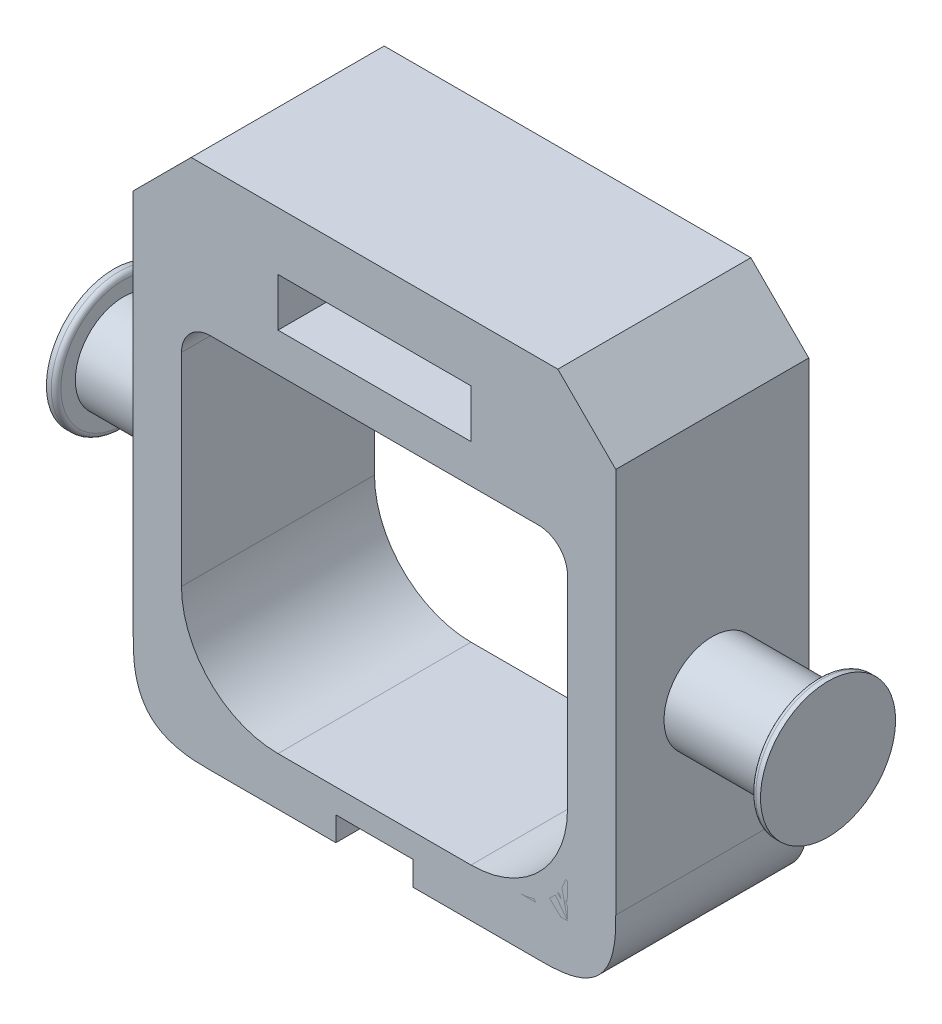
SolidWorks part; units mm, degrees
ref_plane "Front Plane" through (0, 0, 0) normal (0, 0, 1) x (1, 0, 0)
ref_plane "Top Plane" through (0, 0, 0) normal (0, 1, 0) x (1, 0, 0)
ref_plane "Right Plane" through (0, 0, 0) normal (1, 0, 0) x (0, 0, -1)
sketch "Sketch1" plane through (0, 0, 0) normal (0, 0, 1) x (1, 0, 0)
  line L0 (-20, 0) -> (0, 0)
  line L1 (0, 0) -> (0, -17)
  line L2 (0, -17) -> (-20, -17)
  line L3 (-20, -17) -> (-20, 0)
  line L4 (-22.5, 7.5) -> (-22.5, -19.5)
  line L5 (-22.5, -19.5) -> (2.5, -19.5)
  line L6 (2.5, -19.5) -> (2.5, 7.5)
  line L7 (-22.5, 7.5) -> (2.5, 7.5)
  dimension "D1" = 20
  dimension "D2" = 17
  dimension "D3" = 7.5
  dimension "D4" = 27
  dimension "D5" = 25
  dimension "D6" = 2.5
extrude "Boss-Extrude1" add sketch "Sketch1" along normal blind 10
fillet "Fillet1" radius 4 2 edges at (-22.5, -19.5, 5) (2.5, -19.5, 5) curvature continuous yes
ref_plane "Plane1" through (-20, -17, 10) normal (0, -1, 0) x (-1, 0, 0)
sketch "Sketch3" plane through (0, 0, 10) normal (0, 0, 1) x (1, 0, 0)
  line L1 (0, 0) -> (-10, -17)
  line L2 (-21.65, -17) -> (-18.35, -17) construction
  line L3 (-20, 0) -> (-20, -1.5)
  line L4 (-20, 0) -> (-20, -17) construction
  line L5 (-20, 0) -> (-18.5, 0)
  arc A0 (-20, -1.5) -> (-18.5, 0) centre (-18.5, -1.5) cw
  line M13 (-20, -17) -> (-20, 0)
  line M14 (-20, 0) -> (0, 0)
extrude "Boss-Extrude2" add sketch "Sketch3" against normal blind 10 contours A0 M13 M14 region at (-19.6649, -0.3351, 10)
sketch "Sketch4" plane through (0, 0, 10) normal (0, 0, 1) x (1, 0, 0)
  line L0 (0, 0) -> (0, -1.4954)
  line L1 (0, -17) -> (0, 0) construction
  line L2 (0, 0) -> (-1.4954, 0)
  line L3 (0, 0) -> (-18.5, 0) construction
  arc A0 (0, -1.4954) -> (-1.4954, 0) centre (-1.4954, -1.4954) ccw
extrude "Boss-Extrude3" add sketch "Sketch4" against normal blind 10
sketch "Sketch6" plane through (0, 0, 10) normal (0, 0, 1) x (1, 0, 0)
  line L0 (0, -17) -> (0, -14.5)
  line L1 (0, -17) -> (0, -1.4954) construction
  line L2 (0, -17) -> (-2.5, -17)
  line L3 (-20, -17) -> (0, -17) construction
  arc A0 (-2.5, -17) -> (0, -14.5) centre (-2.5, -14.5) ccw
extrude "Boss-Extrude4" add sketch "Sketch6" against normal blind 7.5 separate body
sketch "Sketch7" plane through (0, 0, 10) normal (0, 0, 1) x (1, 0, 0)
  line L0 (-20, -17) -> (-15, -17)
  line L1 (-21.65, -17) -> (-18.35, -17) construction
  line L2 (-20, -1.5) -> (-20, -17) construction
  line L3 (-20, -17) -> (-20, -12)
  line L4 (0, -17) -> (-5, -17)
  line L5 (-20, -17) -> (0, -17) construction
  line L6 (0, -17) -> (0, -12)
  line L7 (0, -17) -> (0, -1.4954) construction
  arc A0 (-15, -17) -> (-20, -12) centre (-15, -12) cw
  arc A1 (-5, -17) -> (0, -12) centre (-5, -12) ccw
extrude "Boss-Extrude5" add sketch "Sketch7" against normal blind 10
chamfer "Chamfer1" distance 3 angle 45 2 edges at (2.5, 7.5, 5) (-22.5, 7.5, 5)
sketch "Sketch8" plane through (0, 0, 10) normal (0, 0, 1) x (1, 0, 0)
  line L0 (-15, 4.5) -> (-5, 4.5)
  line L1 (-5, 4.5) -> (-5, 2)
  line L2 (-5, 2) -> (-15, 2)
  line L3 (-15, 2) -> (-15, 4.5)
  line L4 (-0.5, 7.5) -> (-19.5, 7.5) construction
  line L8 (-22.5, 4.5) -> (-22.5, -15.5) construction
  dimension "D1" = 7.5
  dimension "D2" = 3
  dimension "D3" = 2.5
extrude "Cut-Extrude1" cut sketch "Sketch8" against normal blind 10.5 contours L3 L2 L1 L0 region at (-10, 3.25, 10)
sketch "Sketch9" plane through (0, 0, 10) normal (0, 0, 1) x (1, 0, 0)
  line L0 (-18.5, -19.5) -> (-1.5, -19.5) construction
  line L1 (-6.1419, -18.5) -> (-4.1419, -18.5)
  line L2 (-6.1419, -18.5) -> (-6.1419, -19.5)
  line L3 (-6.1419, -19.5) -> (-4.1419, -19.5)
  line L4 (-4.1419, -18.5) -> (-4.1419, -19.5)
  dimension "D1" = 1
sketch "Sketch12" plane through (0, 0, 0) normal (0, 0, -1) x (-1, 0, 0)
  line L10 (19.5, 7.5) -> (0.5, 7.5)
  line L11 (0.5, 7.5) -> (-2.5, 4.5)
  line L12 (-2.5, 4.5) -> (-2.5, -15.5)
  line L13 (1.5, -19.5) -> (18.5, -19.5)
  line L14 (22.5, -15.5) -> (22.5, 4.5)
  line L15 (22.5, 4.5) -> (19.5, 7.5)
  line L18 (-2.5, 4.5) -> (-2.5, -15.5)
  spline S2 degree 2 poles (67.845, 982.0209) (-3.6492, 1.7622) (-2.4812, -16.3302) (-2.4524, -16.7775) (-2.3691, -17.1519) (-2.1636, -18.0767) (-1.6244, -18.6183) (-1.0848, -19.1602) (-0.1577, -19.3678) (0.2161, -19.4515) (0.6646, -19.4809) (18.738, -20.6634) (998.9799, 51.3297) knots -7.651516 -7.651516 -7.651516 0.125 0.125 0.25 0.25 0.5 0.5 0.75 0.75 0.875 0.875 8.610168 8.610168 8.610168 only from (-2.5, -15.5) to (1.5, -19.5)
  spline S3 degree 2 poles (-979.0209, 50.845) (1.2378, -20.6492) (19.3302, -19.4812) (19.7775, -19.4524) (20.1519, -19.3691) (21.0767, -19.1636) (21.6183, -18.6244) (22.1602, -18.0848) (22.3678, -17.1577) (22.4515, -16.7839) (22.4809, -16.3354) (23.6634, 1.738) (-48.3297, 981.9799) knots -7.651516 -7.651516 -7.651516 0.125 0.125 0.25 0.25 0.5 0.5 0.75 0.75 0.875 0.875 8.610168 8.610168 8.610168 only from (18.5, -19.5) to (22.5, -15.5)
  dimension "D1" = 0
ref_plane "Plane2" through (-10, 0, 0) normal (-1, 0, 0) x (0, 0, 1)
sketch "Sketch19" plane through (0, 0, 10) normal (0, 0, 1) x (1, 0, 0)
  line L0 (-18.5, -19.5) -> (-1.5, -19.5) construction
  line L1 (-12, -18.25) -> (-8, -18.25)
  line L2 (-12, -18.25) -> (-12, -19.5)
  line L3 (-12, -19.5) -> (-8, -19.5)
  line L4 (-8, -18.25) -> (-8, -19.5)
  line L5 (-22.5, 4.5) -> (-22.5, -15.5) construction
  dimension "D1" = 10.5
  dimension "D2" = 4
extrude "Cut-Extrude5" cut sketch "Sketch19" against normal through all
sketch "Sketch20" plane through (2.5, 0, 0) normal (1, 0, 0) x (0, 0, -1)
  circle A0 centre (-5, -8) radius 2.5
extrude "Boss-Extrude10" add sketch "Sketch20" along normal blind 6
sketch "Sketch21" plane through (8.5, 0, 0) normal (1, 0, 0) x (0, 0, -1)
  circle A0 centre (-5, -8) radius 3.5
extrude "Boss-Extrude11" add sketch "Sketch21" against normal blind 0.5
fillet "Fillet2" radius 0.25 1 edges at (8, -8, 1.5)
mirror "Mirror1" about plane through (-10, 0, 0) normal (-1, 0, 0) of "Boss-Extrude11", "Boss-Extrude10"
fillet "Fillet3" radius 0.25 1 edges at (-28, -8, 1.5)
